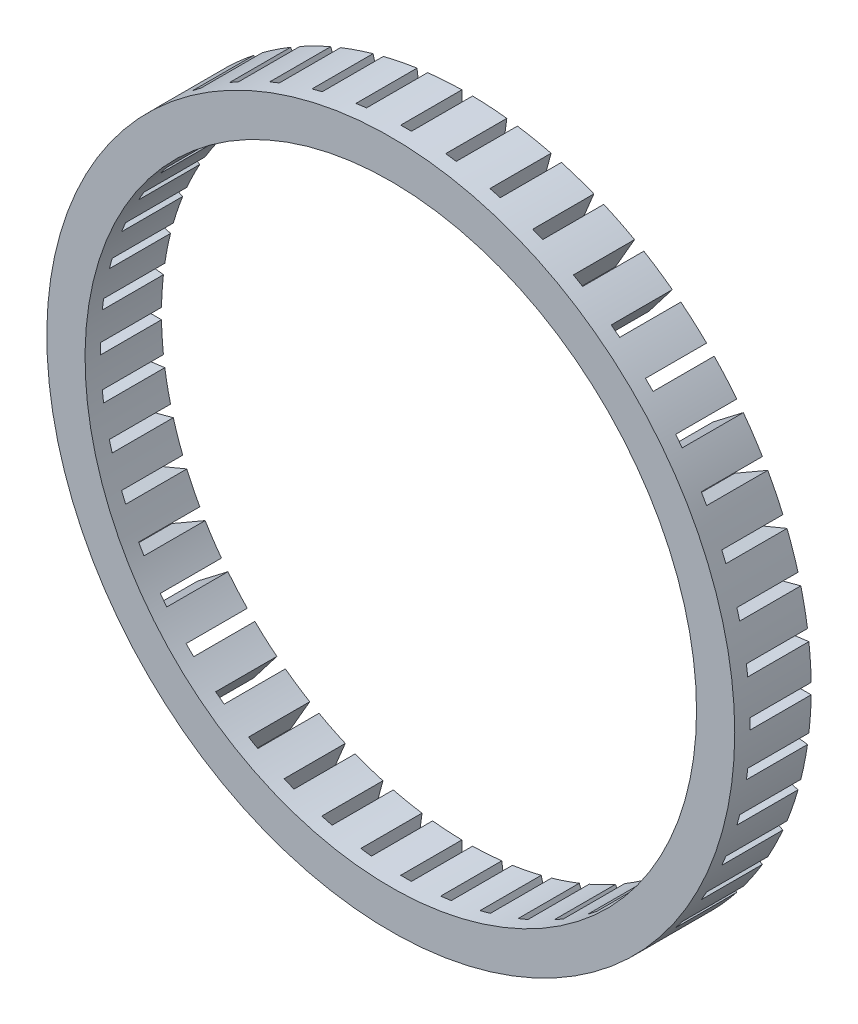
SolidWorks part; units mm, degrees
ref_plane "Front Plane" through (0, 0, 0) normal (0, 0, 1) x (1, 0, 0)
ref_plane "Top Plane" through (0, 0, 0) normal (0, 1, 0) x (1, 0, 0)
ref_plane "Right Plane" through (0, 0, 0) normal (1, 0, 0) x (0, 0, -1)
sketch "Sketch1" plane through (0, 0, 0) normal (0, 0, 1) x (1, 0, 0)
  circle A0 centre (0, 0) radius 40
  circle A1 centre (0, 0) radius 45
  dimension "D1" = 80
  dimension "D2" = 90
extrude "Boss-Extrude1" add sketch "Sketch1" along normal blind 10 contours A1 | A0
sketch "Sketch2" plane through (0, 0, 10) normal (0, 0, 1) x (1, 0, 0)
  line L0 (0, 0) -> (0, 45)
  circle A1 centre (0, 0) radius 45 construction
sketch "Sketch3" plane through (0, 0, 0) normal (0, 1, 0) x (1, 0, 0)
  line L0 (-0.7, 0) -> (-0.7, -8)
  line L1 (-0.7, -8) -> (0.7, -8)
  line L2 (0.7, -8) -> (0.7, 0)
  line L3 (0.7, 0) -> (-0.7, 0)
  point P2 (0, 0)
  dimension "D1" = 8
  dimension "D2" = 1.4
extrude "Cut-Extrude1" cut sketch "Sketch3" against normal through all both and the other way through all
ref_axis "Axis2" through (0, 0, -0.5) along (0, 0, 1)
pattern_circular "CirPattern1" count 48 over 360 about axis through (0, 0, -0.5) along (0, 0, 1) of "Cut-Extrude1"
